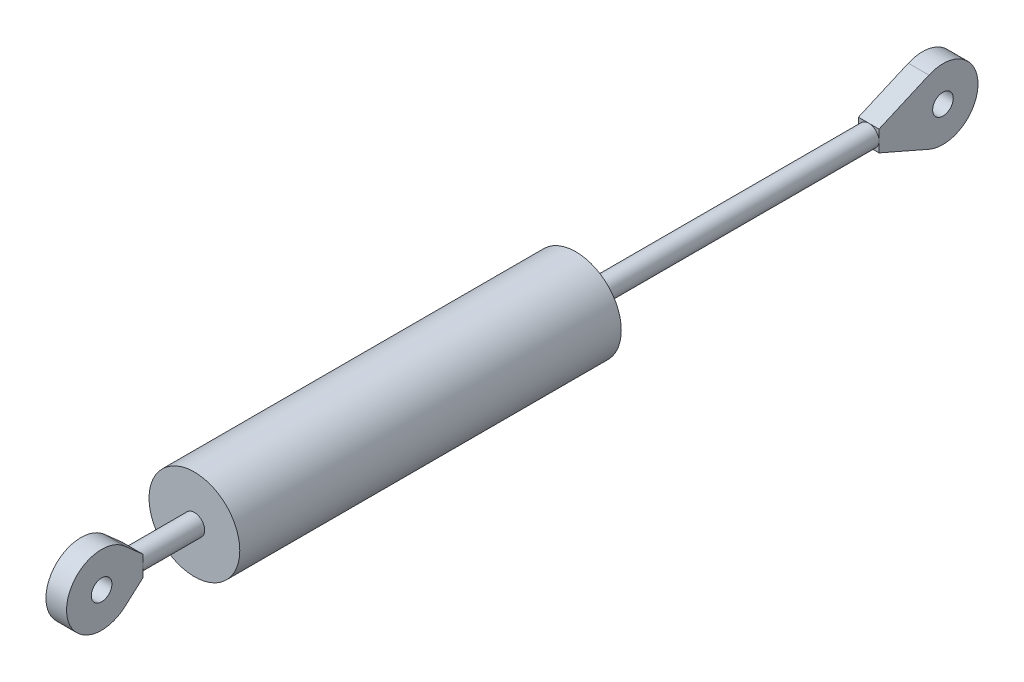
SolidWorks part; units mm, degrees
ref_plane "Front Plane" through (0, 0, 0) normal (0, 0, 1) x (1, 0, 0)
ref_plane "Top Plane" through (0, 0, 0) normal (0, 1, 0) x (1, 0, 0)
ref_plane "Right Plane" through (0, 0, 0) normal (1, 0, 0) x (0, 0, -1)
sketch "Sketch1" plane through (0, 0, 0) normal (1, 0, 0) x (0, 0, -1)
  line L0 (-46.25, 0) -> (46.25, 0)
  line L1 (-46.25, 11) -> (46.25, 11)
  line L2 (-46.25, 11) -> (-46.25, 0)
  line L4 (46.25, 11) -> (46.25, 0)
  line L5 (-46.25, 11) -> (0, 0) construction
  line L6 (0, 0) -> (46.25, 11) construction
  point P0 (0, 0)
  dimension "D1" = 92.5
  dimension "D2" = 11
revolve "Revolve1" add sketch "Sketch1" angle 360 about L0
sketch "Sketch2" plane through (0, 0, 46.25) normal (0, 0, 1) x (1, 0, 0)
  circle A0 centre (0, 0) radius 2.5
  dimension "D1" = 5
extrude "Boss-Extrude1" add sketch "Sketch2" along normal blind 15
sketch "Sketch3" plane through (0, 0, 0) normal (1, 0, 0) x (0, 0, -1)
  line L0 (-46.25, 11) -> (-46.25, -11) construction
  line L1 (-61.25, 2.5) -> (-65.6162, 6.3648)
  line L2 (-61.25, -2.5) -> (-65.6162, -6.3648)
  line L3 (-61.25, 2.5) -> (-61.25, -2.5)
  arc A0 (-65.6162, 6.3648) -> (-65.6162, -6.3648) centre (-71.25, 0) ccw
  circle A1 centre (-71.25, 0) radius 2.5
  dimension "D1" = 17
  dimension "D2" = 5
  dimension "D3" = 25
extrude "Boss-Extrude2" add sketch "Sketch3" along normal blind 2.5 and the other way blind 2.5
sketch "Sketch4" plane through (0, 0, -46.25) normal (0, 0, -1) x (-1, 0, 0)
  circle A0 centre (0, 0) radius 2.5
  dimension "D1" = 5
extrude "Boss-Extrude3" add sketch "Sketch4" along normal blind 71
sketch "Sketch5" plane through (0, 0, 0) normal (1, 0, 0) x (0, 0, -1)
  line L4 (46.25, -11) -> (46.25, 11) construction
  line L5 (0, 0) -> (112.0554, 0) construction
  line L6 (117.25, 2.5) -> (129.3449, 7.7881)
  line L7 (117.25, 2.5) -> (117.25, -2.5)
  line L8 (117.25, -2.5) -> (129.3449, -7.7881)
  circle A1 centre (132.75, 0) radius 2.5
  arc A2 (129.3449, -7.7881) -> (129.3449, 7.7881) centre (132.75, 0) ccw
  dimension "D1" = 8.5
  dimension "D2" = 5
  dimension "D3" = 86.5
extrude "Boss-Extrude4" add sketch "Sketch5" along normal blind 2.5 and the other way blind 2.5
